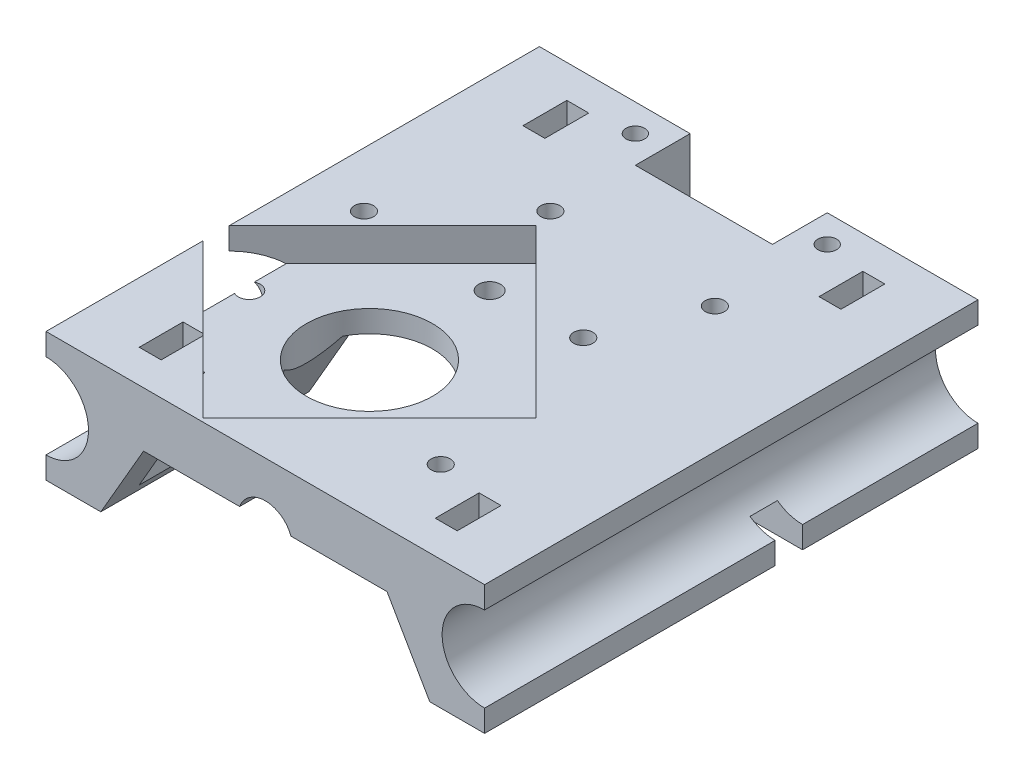
SolidWorks part; units mm, degrees
material "ABS"
ref_plane "Plano frontal" through (0, 0, 0) normal (0, 0, 1) x (1, 0, 0)
ref_plane "Plano superior" through (0, 0, 0) normal (0, 1, 0) x (1, 0, 0)
ref_plane "Plano direito" through (0, 0, 0) normal (1, 0, 0) x (0, 0, -1)
sketch "Esboço1" plane through (0, 0, 0) normal (0, 0, 1) x (1, 0, 0)
  line L0 (40, 0) -> (-40, 0)
  line L1 (-40, -19.5) -> (-40, -23.5)
  line L2 (-40, -23.5) -> (-30, -23.5)
  line L3 (-30, -23.5) -> (-22.2058, -10)
  line L4 (-22.2058, -10) -> (-4.6837, -10)
  line L5 (-40, 0) -> (-40, -4)
  line L6 (0, 0) -> (0, -46.1263) construction
  line L7 (40, 0) -> (40, -4)
  line L8 (30, -23.5) -> (22.2058, -10)
  line L9 (40, -23.5) -> (30, -23.5)
  line L10 (40, -19.5) -> (40, -23.5)
  line L11 (4.6837, -10) -> (22.2058, -10)
  line L12 (-40, -11.75) -> (40, -11.75) construction
  arc A0 (-40, -4) -> (-40, -19.5) centre (-40, -11.75) cw
  arc A1 (40, -4) -> (40, -19.5) centre (40, -11.75) ccw
  arc A2 (4.6837, -10) -> (-4.6837, -10) centre (0, -11.75) ccw
  point P17 (0, -12.2866)
  point P21 (0, 0)
  dimension "D1" = 7.75
  dimension "D7" = 5
  dimension "D2" = 4
  dimension "D3" = 60
  dimension "D4" = 10
  dimension "D5" = 10
  dimension "D6" = 40
extrude "Ressalto-extrusão1" add sketch "Esboço1" along normal blind 90
sketch "Esboço2" plane through (0, 0, 0) normal (0, 1, 0) x (1, 0, 0)
  line L1 (-42.4056, -59) -> (-12, -28.5944)
  line L2 (-42.4056, -59) -> (-12, -89.4056)
  line L3 (-12, -89.4056) -> (18.4056, -59)
  line L4 (-12, -28.5944) -> (18.4056, -59)
  line L5 (-42.4056, -59) -> (18.4056, -59) construction
  line L6 (-12, -89.4056) -> (-12, -28.5944) construction
  line L8 (-40, -90) -> (-40, 0) construction
  line L9 (40, -90) -> (-40, -90) construction
  line L11 (-22.2058, -90) -> (-4.6837, -90) construction
  circle A0 centre (-12, -59) radius 5
  point P0 (-12, -59)
  dimension "D4" = 10
  dimension "D1" = 43
  dimension "D2" = 28
  dimension "D3" = 31
extrude "Corte-extrusão1" cut sketch "Esboço2" against normal offset from surface (6 mm away) 4 up to face at (-13.4448, -10, 45)
sketch "Esboço3" plane through (0, -6, 0) normal (0, 1, 0) x (1, 0, 0)
  line L2 (-6.7523, -61.9088) -> (5.6269, -39.576) construction
  line L3 (-17.6288, -61.0776) -> (-25.3093, -40.2687) construction
  line L4 (-12, -37.0797) -> (9.9203, -59) construction
  line L5 (-12, -37.0797) -> (-33.9203, -59) construction
  line L6 (-33.9203, -59) -> (-12, -80.9203) construction
  line L7 (9.9203, -59) -> (-12, -80.9203) construction
  line L8 (-12, -37.0797) -> (-12, -80.9203) construction
  line L9 (-33.9203, -59) -> (9.9203, -59) construction
  line L10 (40, -90) -> (-40, -90) construction
  line L13 (-12, -28.5944) -> (-40, -56.5944) construction
  line L14 (4.6837, -90) -> (22.2058, -90) construction
  line L16 (-12.5, -10) -> (12.5, -10)
  line L17 (-12.5, -10) -> (-12.5, 0)
  line L18 (-12.5, 0) -> (12.5, 0)
  line L19 (12.5, -10) -> (12.5, 0)
  line L20 (-12.5, -10) -> (12.5, 0) construction
  line L21 (-12.5, 0) -> (12.5, -10) construction
  line L22 (0, -12.8859) -> (0, -1.9558) construction
  line L24 (18.4056, -59) -> (-12, -28.5944) construction
  circle A0 centre (-12, -37.0797) radius 2
  circle A1 centre (9.9203, -59) radius 2
  circle A2 centre (-12, -80.9203) radius 2
  circle A3 centre (-33.9203, -59) radius 2
  circle A4 centre (-12, -59) radius 11.5
  arc A5 (-17.6288, -61.0776) -> (-6.7523, -61.9088) centre (-12, -59) ccw construction
  circle A6 centre (-30, -42) radius 1.75
  circle A7 centre (10, -42) radius 1.75
  circle A8 centre (10, -42) radius 5 construction
  circle A9 centre (-30, -42) radius 5 construction
  circle A10 centre (-17.5, -5) radius 1.7
  circle A11 centre (17.5, -5) radius 1.7
  circle A12 centre (17, -75) radius 1.75
  circle A13 centre (-13, -25) radius 1.75
  circle A14 centre (17, -25) radius 1.75
  circle A15 centre (17, -25) radius 7.5 construction
  circle A16 centre (-13, -25) radius 7.5 construction
  circle A17 centre (17, -75) radius 7.5 construction
  point P0 (-11.5, -62)
  point P5 (0, 0)
  point P6 (-12, -59)
  point P29 (0, 0)
  point P38 (0, -5)
  point P60 (17, -75)
  point P66 (12.5, -5)
  dimension "D3" = 23
  dimension "D4" = 12
  dimension "D5" = 3.5
  dimension "D8" = 10
  dimension "D12" = 3.4
  dimension "D13" = 3.5
  dimension "D17" = 15
  dimension "D19" = 4
  dimension "D2" = 31
  dimension "D6" = 48
  dimension "D7" = 40
  dimension "D9" = 10
  dimension "D10" = 25
  dimension "D11" = 17.5
  dimension "D14" = 15
  dimension "D15" = 30
  dimension "D16" = 50
  dimension "D18" = 22
  dimension "D20" = 17
  dimension "D21" = 31
  dimension "D22" = 7
  dimension "D23" = 17
extrude "Corte-extrusão2" cut sketch "Esboço3" against normal through all and the other way through all
sketch "Esboço4" plane through (0, -10, 0) normal (0, -1, 0) x (1, 0, 0)
  line L0 (-44.5112, 37) -> (44.1077, 37)
  line L2 (-44.5112, 37) -> (-44.5112, 32)
  line L3 (-44.5112, 32) -> (44.1077, 32)
  line L4 (44.1077, 32) -> (44.1077, 37)
  circle A0 centre (-30, 42) radius 5 construction
  circle A1 centre (10, 42) radius 5 construction
  point P11 (-28.4465, 37.2475)
  line M8 (-4.6837, 10) -> (-4.6837, 50.1274)
  dimension "D1" = 10
  dimension "D2" = 5
extrude "Corte-extrusão4" cut sketch "Esboço4" against normal blind 12 from offset 20 contours L3 L0 M8 | L2 L3 L0 | L3 L4 L0 M8 region at (-24.5975, -10, 34.5) region at (19.712, -10, 34.5)
sketch "Esboço6" plane through (0, -23.5, 0) normal (0, -1, 0) x (1, 0, 0)
  line L0 (-40, 90) -> (-40, 37) construction
  line L2 (-20, 32) -> (-40, 32)
  line L5 (-20, 32) -> (-20, 52)
  line L6 (-20, 52) -> (-40, 52)
  line L7 (-40, 32) -> (-40, 52)
  line L8 (-20, 32) -> (-40, 52) construction
  line L9 (-20, 52) -> (-40, 32) construction
  line L10 (-30, 32) -> (-40, 32) construction
  circle A0 centre (17, 75) radius 8
  circle A1 centre (17, 25) radius 8
  circle A2 centre (-13, 25) radius 8
  point P0 (-30, 42)
  dimension "D1" = 16
extrude "Corte-extrusão7" cut sketch "Esboço6" against normal up to surface (13.5 mm away) up to face at (-14, -10, 80.9203)
sketch "Esboço7" plane through (0, 0, 0) normal (0, 1, 0) x (1, 0, 0)
  line L0 (-32.25, 0) -> (-32.25, -90) construction
  line L1 (40, -90) -> (-40, -90) construction
  line L3 (32.25, -90) -> (32.25, 0) construction
  line L5 (27.0009, -70) -> (27.0009, -90) construction
  line L6 (40, -90) -> (-40, -90) construction
  line L7 (44.8347, -45) -> (-53.0929, -45) construction
  line L8 (25.0009, -76) -> (29.0009, -76)
  line L9 (25.0009, -76) -> (25.0009, -84)
  line L10 (25.0009, -84) -> (29.0009, -84)
  line L11 (29.0009, -76) -> (29.0009, -84)
  line L12 (25.0009, -76) -> (29.0009, -84) construction
  line L13 (25.0009, -84) -> (29.0009, -76) construction
  line L14 (25.0009, -6) -> (29.0009, -14) construction
  line L15 (25.0009, -14) -> (29.0009, -6) construction
  line L16 (27.0009, -20) -> (27.0009, 0) construction
  line L17 (29.0009, -14) -> (29.0009, -6)
  line L18 (25.0009, -6) -> (29.0009, -6)
  line L19 (25.0009, -14) -> (25.0009, -6)
  line L20 (25.0009, -14) -> (29.0009, -14)
  line L21 (0, 4.9721) -> (0, -101.7412) construction
  line L22 (-27.0009, -20) -> (-27.0009, 0) construction
  line L23 (-25.0009, -14) -> (-29.0009, -6) construction
  line L24 (-25.0009, -6) -> (-29.0009, -14) construction
  line L25 (-25.0009, -84) -> (-29.0009, -76) construction
  line L26 (-25.0009, -76) -> (-29.0009, -84) construction
  line L27 (-27.0009, -70) -> (-27.0009, -90) construction
  line L28 (-25.0009, -14) -> (-29.0009, -14)
  line L29 (-25.0009, -14) -> (-25.0009, -6)
  line L30 (-25.0009, -6) -> (-29.0009, -6)
  line L31 (-29.0009, -14) -> (-29.0009, -6)
  line L32 (-29.0009, -76) -> (-29.0009, -84)
  line L33 (-25.0009, -84) -> (-29.0009, -84)
  line L34 (-25.0009, -76) -> (-25.0009, -84)
  line L35 (-25.0009, -76) -> (-29.0009, -76)
  point P10 (27.0009, -80)
  point P27 (27.0009, -10)
  point P43 (-27.0009, -10)
  point P44 (-27.0009, -80)
  dimension "D1" = 20
  dimension "D2" = 8
  dimension "D3" = 4
extrude "Corte-extrusão8" cut sketch "Esboço7" against normal through all
sketch "Esboço11" plane through (0, -10, 0) normal (0, -1, 0) x (1, 0, 0)
  circle A0 centre (-13, 25) radius 3.5
  circle A1 centre (-13, 25) radius 1.75
  circle A2 centre (17, 25) radius 1.75
  circle A3 centre (17, 25) radius 3.5
  circle A4 centre (17, 75) radius 3.5
  circle A5 centre (17, 75) radius 1.75
  dimension "D1" = 7
extrude "Ressalto-extrusão3" add sketch "Esboço11" along normal blind 12
